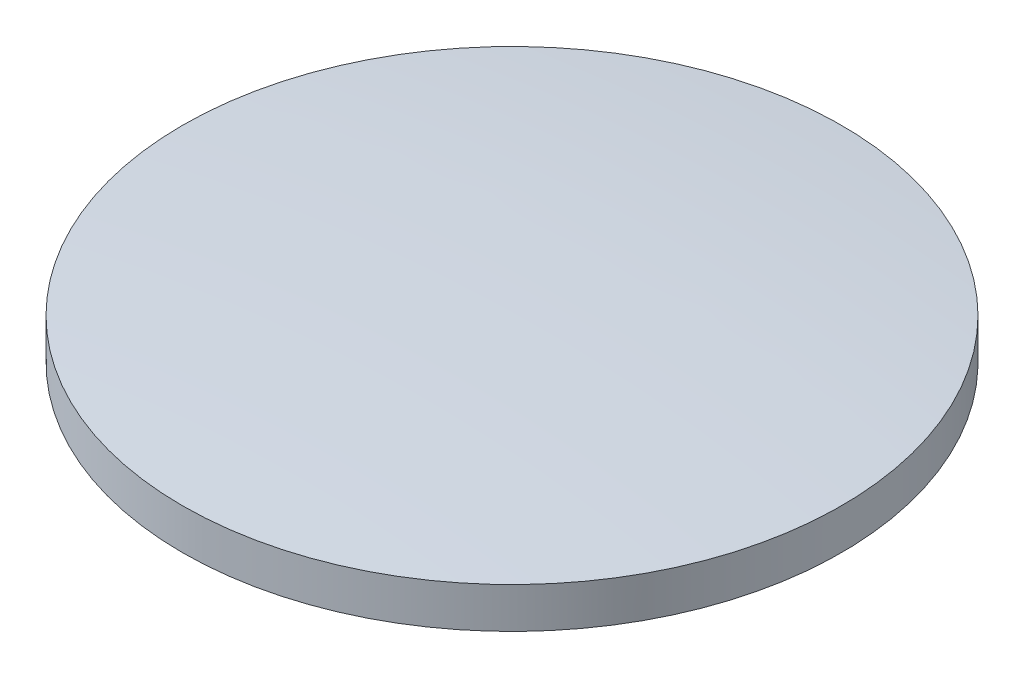
SolidWorks part; units mm, degrees
material "Acrylic (Medium-high impact)"
ref_plane "Front Plane" through (0, 0, 0) normal (0, 0, 1) x (1, 0, 0)
ref_plane "Top Plane" through (0, 0, 0) normal (0, 1, 0) x (1, 0, 0)
ref_plane "Right Plane" through (0, 0, 0) normal (1, 0, 0) x (0, 0, -1)
sketch "Sketch1" plane through (0, 0, 0) normal (0, 0, 1) x (1, 0, 0)
  line L0 (0, 0) -> (-25.95, 0)
  line L1 (-25.95, 0) -> (-25.95, 3.2)
  line L2 (-25.95, 3.2) -> (0, 3.2) construction
  line L3 (0, 3.2) -> (0, 0)
  line L4 (0, 3.2) -> (0, 4.4)
  line L5 (0, 4.4) -> (-6.7786, 4.4) construction
  arc A0 (0, 4.4) -> (-25.95, 3.2) centre (0, -276.7844) ccw
  dimension "D1" = 25.95
  dimension "D2" = 4.4
  dimension "D3" = 1.2
revolve "Revolve1" add sketch "Sketch1" angle 360 about L3
ref_axis "Axis1" through (0, 0, 0) along (0, 1, 0)
